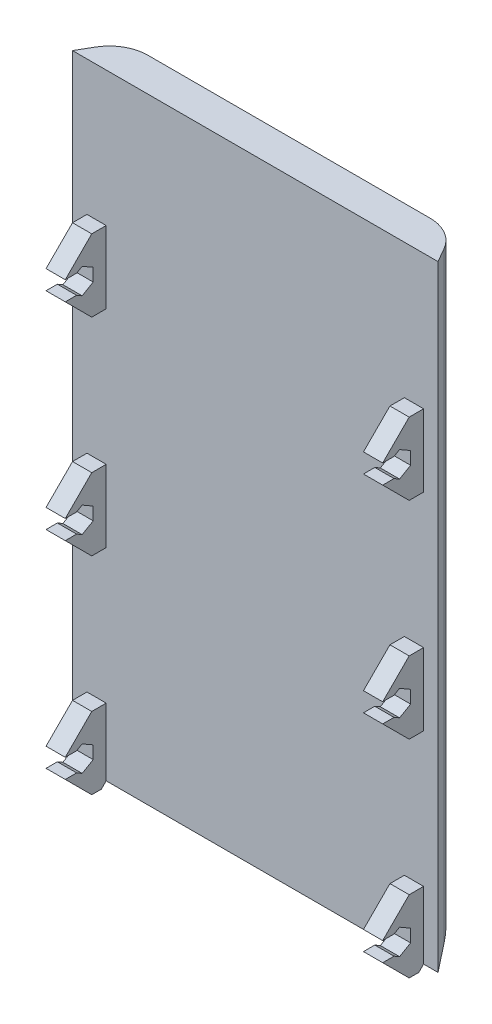
SolidWorks part; units mm, degrees
ref_plane "Front Plane" through (0, 0, 0) normal (0, 0, 1) x (1, 0, 0)
ref_plane "Top Plane" through (0, 0, 0) normal (0, 1, 0) x (1, 0, 0)
ref_plane "Right Plane" through (0, 0, 0) normal (1, 0, 0) x (0, 0, -1)
sketch "Sketch1" plane through (0, 0, 0) normal (0, 1, 0) x (1, 0, 0)
  line L0 (-9.2151, 0) -> (-9.2151, -10)
  line L1 (-9.2151, -10) -> (-5.2151, -10)
  line L2 (-5.2151, -10) -> (-5.2151, 0)
  line L3 (-5.2151, 0) -> (56.7849, 0)
  line L4 (56.7849, 0) -> (56.7849, -10)
  line L5 (56.7849, -10) -> (60.7849, -10)
  line L6 (60.7849, -10) -> (60.7849, 0)
  line L7 (60.7849, 0) -> (63.7849, 0)
  line L8 (-9.2151, 0) -> (-12.2151, 0)
  line L9 (-12.2151, 0) -> (-8.1737, 7)
  line L10 (-8.1737, 7) -> (59.7434, 7)
  line L11 (59.7434, 7) -> (63.7849, 0)
  line L12 (25.7849, 7) -> (25.7849, 0) construction
  dimension "D1" = 3
  dimension "D2" = 10
  dimension "D3" = 70
  dimension "D4" = 7
  dimension "D5" = 4
  dimension "D6" = 60
extrude "Boss-Extrude1" add sketch "Sketch1" along normal blind 129
sketch "Sketch4" plane through (60.7849, 0, 0) normal (1, 0, 0) x (0, 0, -1)
  line L0 (0, 129) -> (0, 0) construction
  line L1 (-37.5185, 129) -> (0, 129)
  line L2 (-37.5185, 129) -> (-37.5185, 101)
  line L3 (-37.5185, 101) -> (0, 101)
  line L4 (0, 129) -> (0, 101)
  line L5 (-37.5185, 129) -> (0, 101) construction
  line L6 (-37.5185, 101) -> (0, 129) construction
  line L7 (-10, 129) -> (0, 129) construction
  point P0 (-18.7592, 115)
  dimension "D1" = 28
extrude "Cut-Extrude1" cut sketch "Sketch4" against normal through all
sketch "Sketch5" plane through (60.7849, 0, 0) normal (1, 0, 0) x (0, 0, -1)
  line L0 (0, 129) -> (0, 0) construction
  line L1 (-33.3149, 86) -> (0, 86)
  line L2 (-33.3149, 86) -> (-33.3149, 58)
  line L3 (-33.3149, 58) -> (0, 58)
  line L4 (0, 86) -> (0, 58)
  line L5 (-33.3149, 86) -> (0, 58) construction
  line L6 (-33.3149, 58) -> (0, 86) construction
  line L7 (-10, 101) -> (0, 101) construction
  point P0 (-16.6574, 72)
  dimension "D1" = 28
  dimension "D2" = 15
extrude "Cut-Extrude2" cut sketch "Sketch5" against normal through all
sketch "Sketch6" plane through (0, 0, 0) normal (1, 0, 0) x (0, 0, -1)
  line L0 (-10, 101) -> (-10, 86) construction
  line L1 (-2.7, 94.8279) -> (-5, 96.1558)
  line L2 (-5, 96.1558) -> (-7.3, 94.8279)
  line L3 (-7.3, 94.8279) -> (-7.3, 92.1721)
  line L4 (-7.3, 92.1721) -> (-5, 90.8442)
  line L5 (-5, 90.8442) -> (-2.7, 92.1721)
  line L6 (-2.7, 92.1721) -> (-2.7, 94.8279)
  line L7 (-10, 101) -> (0, 101) construction
  line L8 (-6.15, 95.4919) -> (-10, 95.4919)
  line L9 (-6.15, 91.5081) -> (-10, 91.5081)
  line L10 (-10, 91.5081) -> (-10, 95.4919)
  circle A1 centre (-5, 93.5) radius 2.3 construction
  dimension "D1" = 4.6
  dimension "D2" = 7.5
  dimension "D3" = 5
extrude "Cut-Extrude3" cut sketch "Sketch6" against normal through all and the other way through all contours L10 L9 L4 L3 L2 L8 | L5 L6 L1 L2 L3 L4 region at (0, 93.5, 5) region at (0, 93.5, 8.5351)
pattern_linear "LPattern1" count 4 spacing 43 along (0, -1, 0) of "Cut-Extrude2", "Cut-Extrude3"
chamfer "Chamfer6" distance 8 angle 45 1 edges at (25.7849, 0, -7)
fillet "Fillet1" radius 8 2 edges at (-8.1737, 68.5, -7) (59.7434, 68.5, -7)
chamfer "Chamfer5" distance 7 angle 45 12 edges at (58.7849, 101, 10) (58.7849, 86, 10) (-7.2151, 101, 10) (-7.2151, 86, 10) (-7.2151, 58, 10) (-7.2151, 43, 10) (58.7849, 58, 10) (58.7849, 43, 10) (58.7849, 15, 10) (58.7849, 0, 10) (-7.2151, 0, 10) (-7.2151, 15, 10)
sketch "Sketch7" plane through (0, 0, -7) normal (0, 0, -1) x (-1, 0, 0)
  line L0 (-40.1246, 129) -> (-40.1246, 21.6303) construction
  line L1 (-55.1246, 129) -> (3.5549, 129) construction
  line L3 (-55.1246, 129) -> (-55.1246, 8) construction
  text T0 "ROaB LaB" font "VALORANT" height in points 48
  point P4 (-40.1246, 21.6303)
  point P9 (0, 0)
  dimension "D1" = 15
extrude "Cut-Extrude4" cut sketch "Sketch7" against normal blind 1
